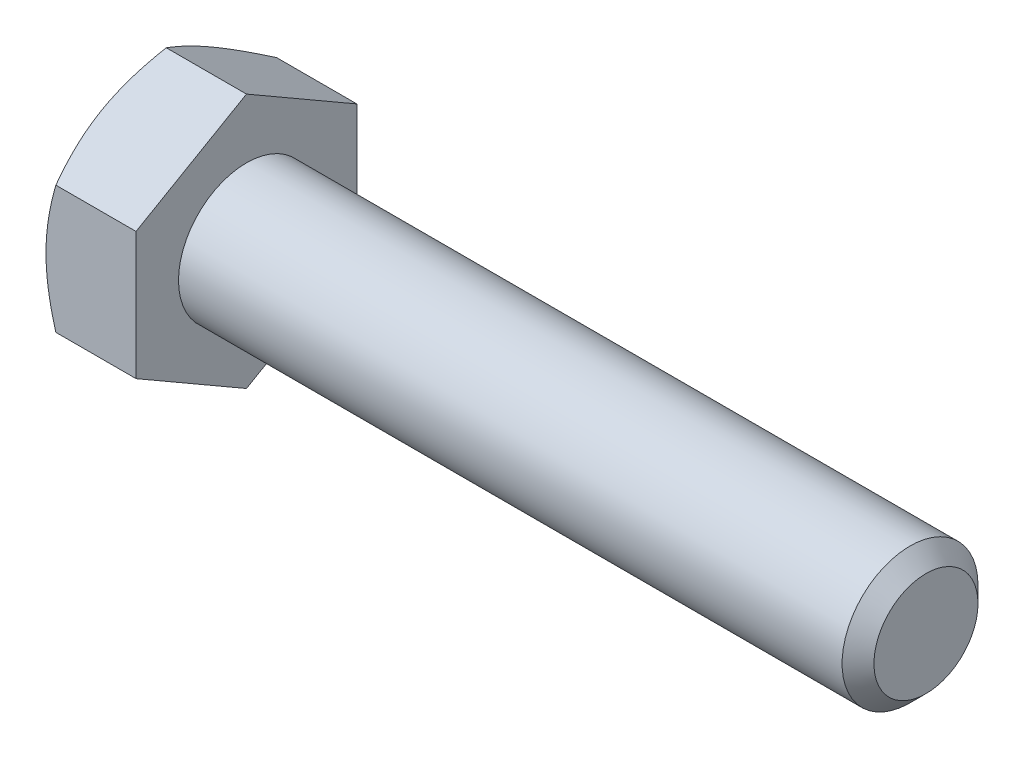
SolidWorks part; units mm, degrees
material "Alloy Steel"
ref_plane "Front Plane" through (0, 0, 0) normal (0, 0, 1) x (1, 0, 0)
ref_plane "Top Plane" through (0, 0, 0) normal (0, 1, 0) x (1, 0, 0)
ref_plane "Right Plane" through (0, 0, 0) normal (1, 0, 0) x (0, 0, -1)
sketch "Sketch1" plane through (0, 0, 0) normal (0, 0, 1) x (1, 0, 0)
  line L0 (-22.65, 0) -> (22.65, 0) construction
  line L1 (-17.35, 6.5) -> (-17.35, -6.5) construction
  line L2 (-22.65, 6.5) -> (-22.65, -6.5) construction
  line L3 (22.65, 4) -> (22.65, -4) construction
  point P8 (18.275, -4)
  dimension "Thread Dia" = 8
  dimension "Hex" = 13
  dimension "Head Ht" = 5.3
  dimension "Length" = 40
  dimension "D1" = 4.375
ref_plane "Plane2" through (22.65, 0, 0) normal (1, 0, 0) x (0, 0, -1)
sketch "Sketch2" plane through (22.65, 0, 0) normal (1, 0, 0) x (0, 0, -1)
  circle A0 centre (0, 0) radius 4
extrude "Boss-Extrude1" add sketch "Sketch2" against normal up to vertex (40 mm away) up to point (-17.35, -6.5, 0)
sketch "Sketch4" plane through (22.65, 0, 0) normal (1, 0, 0) x (0, 0, -1)
  circle A1 centre (0, 0) radius 4
  circle A2 centre (0, 0) radius 4
  dimension "D1" = 0
curve "Helix/Spiral1" [suppressed] pitch 1.25 height 41.25 turns 33 parameters "Pitch"=1.25
chamfer "Chamfer1" distance 0.9375 angle 45 1 edges at (22.65, 0, -4)
sketch "Sketch5" plane through (0, 0, 0) normal (0, 0, 1) x (1, 0, 0)
  line L0 (22.65, 4) -> (23.1188, 3.1881)
  line L1 (23.1188, 3.1881) -> (23.275, 3.1881)
  line L2 (23.275, 3.1881) -> (23.7437, 4)
  line L3 (22.65, 4) -> (23.7437, 4)
  line L4 (23.1969, 3.1881) -> (23.1969, 4) construction
  line L5 (22.8844, 3.5941) -> (23.5094, 3.5941) construction
  line L6 (22.65, -4) -> (22.65, 4) construction
  dimension "D1" = 60
  dimension "D2" = 0.1562
  dimension "D3" = 0.625
sweep "Cut-Sweep1" [suppressed] cut profiles "Sketch5" path "Helix/Spiral1"
sketch "Sketch3" plane through (-17.35, 0, 0) normal (-1, 0, 0) x (0, 0, 1)
  line L0 (0, 6.5) -> (0, -6.5) construction
  line L1 (-6.5, -3.7528) -> (0, -7.5056)
  line L2 (0, -7.5056) -> (6.5, -3.7528)
  line L3 (6.5, -3.7528) -> (6.5, 3.7528)
  line L4 (6.5, 3.7528) -> (0, 7.5056)
  line L5 (0, 7.5056) -> (-6.5, 3.7528)
  line L6 (-6.5, 3.7528) -> (-6.5, -3.7528)
  circle A0 centre (0, 0) radius 6.5 construction
extrude "Boss-Extrude2" add sketch "Sketch3" along normal up to vertex (5.3 mm away) up to point (-22.65, -6.5, 0)
sketch "Sketch6" plane through (-22.65, 0, 0) normal (-1, 0, 0) x (0, 0, 1)
  circle A0 centre (0, 0) radius 6.5 construction
  circle A1 centre (0, 0) radius 6.5
extrude "Cut-Extrude1" cut sketch "Sketch6" against normal through all draft 60 flip side to cut
sketch "Sketch7" plane through (-22.65, 0, 0) normal (-1, 0, 0) x (0, 0, 1)
  line L0 (0, 0) -> (0, 6.5) construction
  line L2 (0, 6.5) -> (0, -6.5) construction
  line L3 (-5.6292, 3.25) -> (5.6292, 3.25) construction
  circle A1 centre (0, 0) radius 6.5 construction
  text T0 "10.9" font "Arial" height in points 6
  point P8 (0, 3.25)
extrude "Cut-Extrude2" [suppressed] cut sketch "Sketch7" against normal blind 0.25
sketch "Sketch9" plane through (0, 0, 0) normal (0, 0, 1) x (1, 0, 0)
  line L0 (-17.35, 4) -> (-17.35, 0)
  line L1 (-17.35, 0) -> (4.65, 0)
  line L2 (4.65, 0) -> (0.65, 4)
  line L3 (0.65, 4) -> (-17.35, 4)
  line L4 (-22.65, 0) -> (22.65, 0) construction
  line L5 (-17.35, 6.5) -> (-17.35, -6.5) construction
  line L6 (22.65, 4) -> (22.65, -4) construction
  dimension "D1" = 45
  dimension "MinThreadLg" = 22
revolve "Revolve1" [suppressed] add sketch "Sketch9" angle 360 about L1
equation "\"D2@Sketch5\" = \"Pitch@Helix/Spiral1\"*.125"
equation "\"D3@Sketch5\" = \"Pitch@Helix/Spiral1\"*.50"
equation "\"D3@Helix/Spiral1\" = \"Length@Sketch1\"+\"Pitch@Helix/Spiral1\""
equation "\"D1@Chamfer1\" = \"Pitch@Helix/Spiral1\"*.750"
equation "\"D1@Sketch1\" = \"Pitch@Helix/Spiral1\"*3.50"
